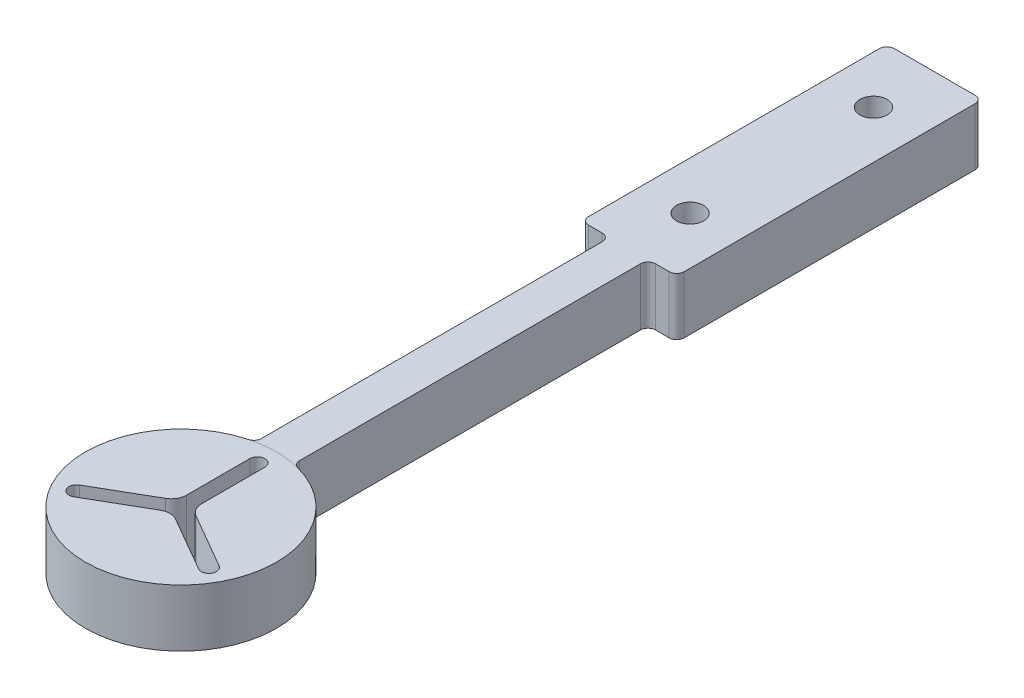
SolidWorks part; units mm, degrees
material "6061-T6 (SS)"
ref_plane "Front Plane" through (0, 0, 0) normal (0, 0, 1) x (1, 0, 0)
ref_plane "Top Plane" through (0, 0, 0) normal (0, 1, 0) x (1, 0, 0)
ref_plane "Right Plane" through (0, 0, 0) normal (1, 0, 0) x (0, 0, -1)
sketch "Sketch1" plane through (0, 0, 0) normal (0, 1, 0) x (1, 0, 0)
  line L0 (-55, 0) -> (55, 0) construction
  line L1 (-7.9375, 50.8) -> (7.9375, 50.8)
  line L2 (-7.9375, 50.8) -> (-7.9375, 0)
  line L3 (-7.9375, 0) -> (-3.175, 0)
  line L4 (7.9375, 50.8) -> (7.9375, 0)
  line L5 (0, -55) -> (0, 55) construction
  line L6 (3.175, 0) -> (7.9375, 0)
  line L8 (-3.175, 0) -> (-3.175, -58.8677)
  line L10 (3.175, 0) -> (3.175, -58.8677)
  arc A0 (-3.175, -58.8677) -> (3.175, -58.8677) centre (0, -74.422) ccw
  dimension "D7" = 31.75
  dimension "D1" = 15.875
  dimension "D2" = 7.9375
  dimension "D3" = 50.8
  dimension "D4" = 74.422
  dimension "D5" = 6.35
  dimension "D6" = 3.175
extrude "Boss-Extrude1" add sketch "Sketch1" along normal blind 9.525
sketch "Sketch2" plane through (0, 9.525, 0) normal (0, 1, 0) x (1, 0, 0)
  line L0 (0, -55) -> (0, 55) construction
  line L1 (7.9375, 50.8) -> (-7.9375, 50.8) construction
  line L2 (-55, 0) -> (55, 0) construction
  circle A0 centre (0, 40.64) radius 2.2479
  circle A1 centre (0, 10.16) radius 2.2479
  dimension "D1" = 4.4958
  dimension "D2" = 4.4958
  dimension "D3" = 10.16
  dimension "D4" = 10.16
extrude "Cut-Extrude1" cut sketch "Sketch2" against normal through all
ref_axis "Axis1" through (0, 11.7998, 74.422) along (0, -1, 0)
sketch "Sketch3" plane through (0, 9.525, 0) normal (0, 1, 0) x (1, 0, 0)
  line L1 (0, -75.8591) -> (10.3762, -81.8499)
  line L3 (-1.2446, -73.7034) -> (-1.2446, -61.722)
  line L4 (1.2446, -73.7034) -> (11.6208, -79.6941)
  line L5 (1.2446, -73.7034) -> (1.2446, -61.722)
  line L6 (0, -5.2388) -> (0, 5.2388) construction
  line L8 (-1.2446, -73.7034) -> (-11.6208, -79.6941)
  line L9 (0, -75.8591) -> (-10.3762, -81.8499)
  line L21 (0, -74.422) -> (-0.6223, -73.3441) [skipped]
  line L22 (0.6223, -73.3441) -> (0, -74.422) [skipped]
  line L23 (0, -74.422) -> (1.2446, -74.422) [skipped]
  arc A0 (-1.2446, -61.722) -> (1.2446, -61.722) centre (0, -61.722) cw
  arc A1 (11.6208, -79.6941) -> (10.3762, -81.8499) centre (10.9985, -80.772) cw
  arc A2 (-10.3762, -81.8499) -> (-11.6208, -79.6941) centre (-10.9985, -80.772) cw
  point P6 (0.6223, -74.422)
  dimension "D1" = 2.4892
  dimension "D2" = 1.2446
  dimension "D4" = 3
extrude "Cut-Extrude2" cut sketch "Sketch3" against normal through all
fillet "Fillet1" radius 1.25 8 edges at (7.9375, 4.7625, -50.8) (-7.9375, 4.7625, -50.8) (-7.9375, 4.7625, 0) (-3.175, 4.7625, 0) (7.9375, 4.7625, 0) (3.175, 4.7625, 0) (3.175, 4.7625, 58.8677) (-3.175, 4.7625, 58.8677)
sketch "Sketch4" plane through (0, 0, 0) normal (0, -1, 0) x (1, 0, 0)
  line L0 (-7.9375, -49.55) -> (-7.9375, -1.25) construction
  line L1 (7.9375, -50.8) -> (-7.9375, -50.8)
  line L2 (7.9375, -50.8) -> (7.9375, 0)
  line L3 (7.9375, 0) -> (-7.9375, 0)
  line L4 (-7.9375, -50.8) -> (-7.9375, 0)
  line L5 (5.2388, 0) -> (-5.2388, 0) construction
  line L6 (7.9375, -1.25) -> (7.9375, -49.55) construction
  line L7 (6.6875, -50.8) -> (-6.6875, -50.8) construction
split line "Split Line1"
sketch "Sketch5" plane through (0, 9.525, 0) normal (0, 1, 0) x (1, 0, 0)
  circle A0 centre (0, -74.422) radius 15.875
split line "Split Line2"
ref_plane "Plane1" through (0, 0, -25.4) normal (0, 0, -1) x (-1, 0, 0)
fillet "Fillet2" radius 2.54 3 edges at (0, 4.7625, 75.8591) (1.2446, 4.7625, 73.7034) (-1.2446, 4.7625, 73.7034)
